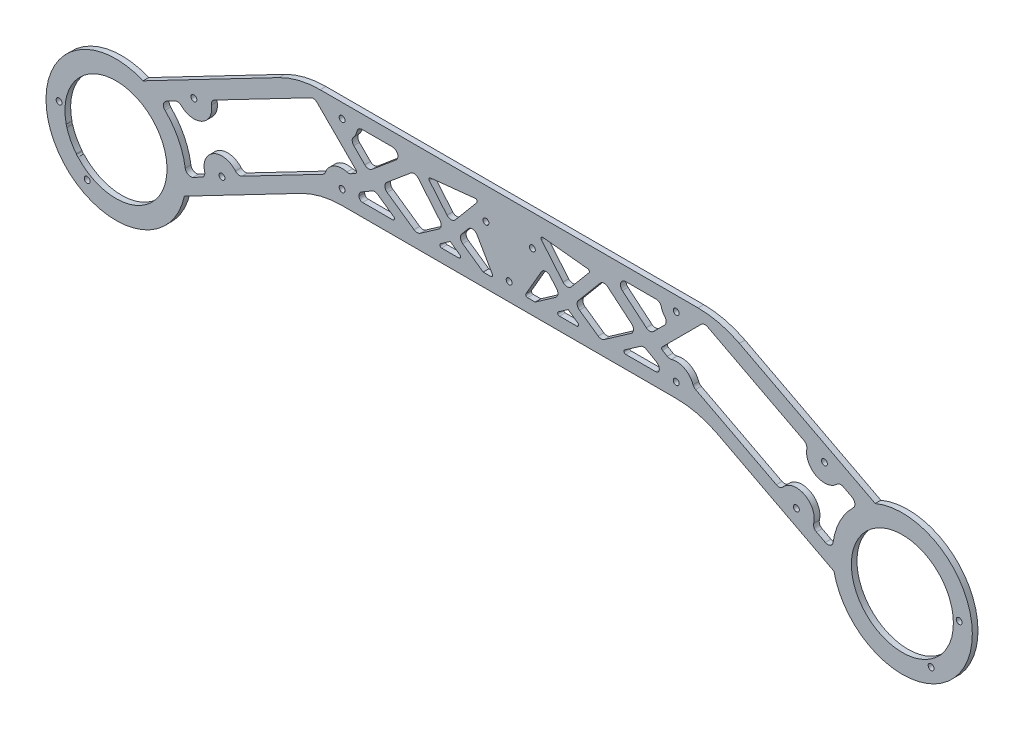
SolidWorks part; units mm, degrees
material "6061-T6 (SS)"
ref_plane "Front Plane" through (0, 0, 0) normal (0, 0, 1) x (1, 0, 0)
ref_plane "Top Plane" through (0, 0, 0) normal (0, 1, 0) x (1, 0, 0)
ref_plane "Right Plane" through (0, 0, 0) normal (1, 0, 0) x (0, 0, -1)
sketch "Sketch1" plane through (0, 0, 0) normal (0, 0, 1) x (1, 0, 0)
  line L0 (0, -33.2132) -> (0, -83.2132) construction
  line L1 (105.7091, -33.2132) -> (-105.7091, -33.2132)
  line L2 (-128.7965, -38.8627) -> (-262.5891, -108.5107)
  line L3 (-262.5891, -108.5107) -> (-239.5017, -152.8612)
  line L4 (-239.5017, -152.8612) -> (-116.5616, -88.8627)
  line L5 (-93.4741, -83.2132) -> (93.4741, -83.2132)
  line L6 (116.5616, -88.8627) -> (239.5017, -152.8612)
  line L7 (239.5017, -152.8612) -> (262.5891, -108.5107)
  line L8 (262.5891, -108.5107) -> (128.7965, -38.8627)
  line L9 (-117.944, -33.2132) -> (0, 28.1845) construction
  line L10 (0, 28.1845) -> (117.944, -33.2132) construction
  line L11 (-251.0454, -130.686) -> (-220, -114.5248) construction
  line L12 (251.0454, -130.686) -> (220, -114.5248) construction
  line L13 (-330, -114.5248) -> (-110, -114.5248) construction
  line L14 (-110, -114.5248) -> (110, -114.5248) construction
  line L15 (0, 0) -> (17.6777, -17.6777) construction
  line L16 (28.2843, -7.0711) -> (7.0711, -28.2843) construction
  line L17 (-7.0711, -28.2843) -> (-17.6777, -17.6777) construction
  line L18 (-17.6777, -17.6777) -> (17.6777, 17.6777) construction
  line L19 (17.6777, 17.6777) -> (28.2843, 7.0711) construction
  line L20 (17.6777, 17.6777) -> (67.5526, 17.6777) construction
  line L21 (0, -35.3553) -> (35.3553, 0) construction
  line L22 (0, 0) -> (6.4705, -24.1481) construction
  line L23 (-8.0184, -28.0304) -> (20.9594, -20.2659) construction
  circle A1 centre (0, 0) radius 7.9375 construction
  circle A2 centre (-220, -114.5248) radius 110 construction
  circle A3 centre (220, -114.5248) radius 110 construction
  arc A4 (28.2843, -7.0711) -> (28.2843, 7.0711) centre (21.2132, 0) ccw construction
  arc A5 (7.0711, -28.2843) -> (-7.0711, -28.2843) centre (0, -21.2132) cw construction
  arc A6 (93.4741, -83.2132) -> (116.5616, -88.8627) centre (93.4741, -133.2132) cw
  arc A7 (-116.5616, -88.8627) -> (-93.4741, -83.2132) centre (-93.4741, -133.2132) cw
  arc A8 (128.7965, -38.8627) -> (105.7091, -33.2132) centre (105.7091, -83.2132) ccw
  arc A9 (-105.7091, -33.2132) -> (-128.7965, -38.8627) centre (-105.7091, -83.2132) ccw
  circle A10 centre (0, 0) radius 7.9375 construction
  arc A11 (20.9594, -20.2659) -> (28.0304, -8.0184) centre (18.3712, -10.6066) ccw construction
  point P26 (17.6777, -17.6777)
  point P33 (35.3553, 0)
  point P36 (0, -35.3553)
  point P40 (0, -31.2132)
  dimension "D12" = 50
  dimension "D2" = 220
  dimension "D1" = 50
  dimension "D3" = 125
  dimension "D5" = 35
  dimension "D8" = 45
  dimension "D10" = 2
extrude "Base" add sketch "Sketch1" along normal blind 3.175
fillet "Fillet1" radius 10 4 edges at (262.5891, -108.5107, 1.5875) (239.5017, -152.8612, 1.5875) (-239.5017, -152.8612, 1.5875) (-262.5891, -108.5107, 1.5875)
sketch "Sketch2" plane through (0, 0, 3.175) normal (0, 0, 1) x (1, 0, 0)
  line L0 (0, -33.2132) -> (0, -83.2132) construction
  line L1 (105.7091, -33.2132) -> (-105.7091, -33.2132) construction
  line L2 (-93.4741, -83.2132) -> (93.4741, -83.2132) construction
  circle A0 centre (0, -58.2132) radius 15 construction
  circle A1 centre (-12.9904, -50.7132) radius 1.65
  circle A2 centre (12.9904, -50.7132) radius 1.65
  circle A3 centre (0, -73.2132) radius 1.65
  point P17 (0, -58.2132)
  dimension "D1" = 30
  dimension "D2" = 3.3
  dimension "D3" = 3
extrude "Adapter Attachment" cut sketch "Sketch2" against normal through all
sketch "Sketch3" plane through (0, 0, 3.175) normal (0, 0, 1) x (1, 0, 0)
  line L0 (-258.6387, -109.7562) -> (-249.1015, -112.7633) construction
  line L1 (-238.2561, -148.9108) -> (-235.249, -139.3736) construction
  line L2 (-251.799, -111.9128) -> (-255.493, -104.8167) construction
  line L3 (-236.0996, -142.0711) -> (-232.4056, -149.1672) construction
  line L4 (-128.7965, -38.8627) -> (-253.719, -103.8932) construction
  line L5 (-230.6316, -148.2437) -> (-116.5616, -88.8627) construction
  line L6 (0, -1.7463) -> (0, 1.7463) construction
  line L7 (-236.0996, -142.0711) -> (-160.7036, -102.8225) construction
  line L8 (-176.4031, -72.6641) -> (-251.799, -111.9128) construction
  line L9 (-93.4741, -83.2132) -> (-93.4741, -75.2132) construction
  line L10 (-93.4741, -83.2132) -> (93.4741, -83.2132) construction
  line L11 (-93.4741, -41.2132) -> (-93.4741, -33.2132) construction
  line L12 (105.7091, -33.2132) -> (-105.7091, -33.2132) construction
  arc A0 (-253.719, -103.8932) -> (-257.9716, -117.3808) centre (-249.1015, -112.7633) ccw construction
  arc A1 (-244.1191, -143.9911) -> (-230.6316, -148.2437) centre (-235.249, -139.3736) ccw construction
  circle A2 centre (-251.799, -111.9128) radius 1.65
  circle A3 centre (-236.0996, -142.0711) radius 1.65
  circle A4 centre (-160.7036, -102.8225) radius 1.65
  circle A5 centre (-176.4031, -72.6641) radius 1.65
  circle A6 centre (-93.4741, -75.2132) radius 1.65
  circle A7 centre (-93.4741, -41.2132) radius 1.65
  circle A8 centre (93.4741, -41.2132) radius 1.65
  circle A9 centre (93.4741, -75.2132) radius 1.65
  circle A10 centre (176.4031, -72.6641) radius 1.65
  circle A11 centre (160.7036, -102.8225) radius 1.65
  circle A12 centre (251.799, -111.9128) radius 1.65
  circle A13 centre (236.0996, -142.0711) radius 1.65
  dimension "D2" = 3.3
  dimension "D1" = 8
  dimension "D4" = 85
extrude "Strut Holes" cut sketch "Sketch3" against normal through all
sketch "Sketch4" plane through (0, 0, 3.175) normal (0, 0, 1) x (1, 0, 0)
  line L0 (-241.4586, -107.7589) -> (-213.2341, -93.0661) construction
  line L1 (-128.7965, -38.8627) -> (-262.5891, -108.5107) construction
  line L2 (0, -1.7463) -> (0, 1.7463) construction
  circle A0 centre (-220, -114.5248) radius 16.05
  circle A1 centre (-220, -114.5248) radius 22.5 construction
  circle A2 centre (-241.4586, -107.7589) radius 2.75
  circle A3 centre (-213.2341, -93.0661) radius 2.75
  circle A4 centre (-198.5414, -121.2906) radius 2.75
  circle A5 centre (-226.7659, -135.9834) radius 2.75
  circle A6 centre (226.7659, -135.9834) radius 2.75
  circle A7 centre (241.4586, -107.7589) radius 2.75
  circle A8 centre (198.5414, -121.2906) radius 2.75
  circle A9 centre (213.2341, -93.0661) radius 2.75
  circle A10 centre (220, -114.5248) radius 16.05
  point P15 (-220, -114.5248)
  dimension "D1" = 32.1
  dimension "D2" = 45
  dimension "D4" = 5.5
  dimension "D3" = 4
extrude "Motor Connection" cut sketch "Sketch4" against normal through all
sketch "Sketch5" plane through (0, 0, 3.175) normal (0, 0, 1) x (1, 0, 0)
  line L0 (0, -1.7463) -> (0, 1.7463) construction
  circle A0 centre (-220, -114.5248) radius 28.55
  circle A1 centre (-220, -114.5248) radius 39.1548
  arc A2 (-253.719, -103.8932) -> (-257.9716, -117.3808) centre (-249.1015, -112.7633) ccw construction
  circle A3 centre (-236.0996, -142.0711) radius 1.65 construction
  circle A4 centre (-251.799, -111.9128) radius 1.65 construction
  circle A5 centre (-236.0996, -142.0711) radius 1.65
  circle A6 centre (-251.799, -111.9128) radius 1.65
  circle A7 centre (251.799, -111.9128) radius 1.65
  circle A8 centre (236.0996, -142.0711) radius 1.65
  circle A9 centre (220, -114.5248) radius 39.1548
  circle A10 centre (220, -114.5248) radius 28.55
  line M20 (253.719, -103.8932) -> (128.7965, -38.8627)
  line M24 (-128.7965, -38.8627) -> (-253.719, -103.8932)
  line M28 (-230.6316, -148.2437) -> (-116.5616, -88.8627)
  line M32 (116.5616, -88.8627) -> (230.6316, -148.2437)
  dimension "D1" = 57.1
extrude "Motor Ring" add sketch "Sketch5" against normal up to surface (3.175 mm away) up to face at (-238.7086, -107.7589, 0)
extrude "Motor Slot" cut sketch "Sketch5<2>" against normal through all contours A0 M24 M28 | A10 M32 M20 region at (-220, -114.5248, 3.175) region at (220, -114.5248, 3.175)
sketch "Sketch5<2>" plane through (0, 0, 3.175) normal (0, 0, 1) x (1, 0, 0) same geometry as "Sketch5"
sketch "Sketch6" plane through (0, 0, 3.175) normal (0, 0, 1) x (1, 0, 0)
  line L0 (-247.6068, -122.1316) -> (-242.0658, -132.7758)
  line L1 (-239.3683, -133.6263) -> (-237.5943, -132.7028)
  line L2 (-236.7437, -130.0053) -> (-242.2847, -119.3612)
  line L3 (-244.9822, -118.5106) -> (-246.7563, -119.4341)
  line L4 (-251.799, -111.9128) -> (-236.0996, -142.0711) construction
  line L5 (-243.9493, -126.992) -> (-111.8265, -58.2132) construction
  line L6 (-111.8265, -58.2132) -> (0, -58.2132) construction
  line L7 (0, -33.2132) -> (0, -83.2132) construction
  line L8 (105.7091, -33.2132) -> (-105.7091, -33.2132) construction
  line L9 (-93.4741, -83.2132) -> (93.4741, -83.2132) construction
  line L10 (-14.5393, -75.9632) -> (-10.2714, -75.9632)
  line L12 (-14.5393, -75.9632) -> (-25.9975, -67.9401)
  line L13 (-26.5749, -63.5543) -> (-22.8888, -59.1614)
  line L14 (-28.1716, -75.9632) -> (-37.8284, -75.9632)
  line L15 (-38.402, -74.1441) -> (-33, -70.3615)
  line L16 (-33, -70.3615) -> (-27.598, -74.1441)
  line L17 (-18.9615, -42.4719) -> (-43.968, -45.1002)
  line L18 (-44.6295, -46.7375) -> (-34.7611, -58.4983)
  line L19 (-30.1648, -58.4983) -> (-18.091, -44.1092)
  line L20 (-50.8755, -48.6282) -> (-38.7485, -63.0805)
  line L21 (-39.3259, -67.4663) -> (-49.7793, -74.7859)
  line L22 (-53.2207, -74.7859) -> (-68.277, -64.2434)
  line L23 (-68.4846, -59.4878) -> (-55.102, -48.2584)
  line L24 (-9.4053, -74.4632) -> (-17.9925, -59.5897)
  line L25 (-14.4193, -51.5382) -> (-1.4289, -74.0382) construction
  line L26 (-64.598, -74.1441) -> (-73.5076, -67.9055)
  line L27 (-76.7283, -67.7649) -> (-82.5, -71.0972)
  line L28 (-84, -73.6953) -> (-84, -73.9632)
  line L29 (-82, -75.9632) -> (-65.1716, -75.9632)
  line L30 (-65.2424, -40.7132) -> (-82.2492, -40.7132)
  line L31 (-86.9487, -50.9163) -> (-80.7761, -57.0888)
  line L32 (-76.7264, -57.2656) -> (-63.3141, -46.0113)
  line L33 (-107.4845, -40.2799) -> (-85.5801, -62.1843)
  line L34 (-85.7872, -63.7574) -> (-88.4538, -65.297)
  line L35 (-110.9911, -39.7402) -> (-164.9696, -67.8396)
  line L36 (-128.7965, -38.8627) -> (-204.814, -78.4349) construction
  line L37 (-186.9131, -79.2627) -> (-191.8231, -81.8187)
  line L38 (-176.8853, -111.2462) -> (-171.9235, -108.6632)
  line L39 (-149.4837, -96.9818) -> (-104.3206, -73.4714)
  line L40 (-181.7266, -122.7854) -> (-116.5616, -88.8627) construction
  line L41 (149.4837, -96.9818) -> (104.3206, -73.4714)
  line L42 (176.8853, -111.2462) -> (171.9235, -108.6632)
  line L43 (186.9131, -79.2627) -> (191.8231, -81.8187)
  line L44 (110.9911, -39.7402) -> (164.9696, -67.8396)
  line L45 (85.7872, -63.7574) -> (88.4538, -65.297)
  line L46 (107.4845, -40.2799) -> (85.5801, -62.1843)
  line L47 (76.7264, -57.2656) -> (63.3141, -46.0113)
  line L48 (86.9487, -50.9163) -> (80.7761, -57.0888)
  line L49 (65.2424, -40.7132) -> (82.2492, -40.7132)
  line L50 (82, -75.9632) -> (65.1716, -75.9632)
  line L51 (84, -73.6953) -> (84, -73.9632)
  line L52 (76.7283, -67.7649) -> (82.5, -71.0972)
  line L53 (64.598, -74.1441) -> (73.5076, -67.9055)
  line L54 (9.4053, -74.4632) -> (17.9925, -59.5897)
  line L55 (68.4846, -59.4878) -> (55.102, -48.2584)
  line L56 (53.2207, -74.7859) -> (68.277, -64.2434)
  line L57 (39.3259, -67.4663) -> (49.7793, -74.7859)
  line L58 (50.8755, -48.6282) -> (38.7485, -63.0805)
  line L59 (30.1648, -58.4983) -> (18.091, -44.1092)
  line L60 (44.6295, -46.7375) -> (34.7611, -58.4983)
  line L61 (18.9615, -42.4719) -> (43.968, -45.1002)
  line L62 (33, -70.3615) -> (27.598, -74.1441)
  line L63 (38.402, -74.1441) -> (33, -70.3615)
  line L64 (28.1716, -75.9632) -> (37.8284, -75.9632)
  line L65 (26.5749, -63.5543) -> (22.8888, -59.1614)
  line L66 (14.5393, -75.9632) -> (25.9975, -67.9401)
  line L67 (14.5393, -75.9632) -> (10.2714, -75.9632)
  line L68 (244.9822, -118.5106) -> (246.7563, -119.4341)
  line L69 (236.7437, -130.0053) -> (242.2847, -119.3612)
  line L70 (239.3683, -133.6263) -> (237.5943, -132.7028)
  line L71 (247.6068, -122.1316) -> (242.0658, -132.7758)
  circle A0 centre (-12.9904, -50.7132) radius 1.65 construction
  circle A1 centre (0, -73.2132) radius 1.65 construction
  arc A2 (-85.1774, -43.061) -> (-87.083, -46.8171) centre (-93.4741, -41.2132) cw
  arc A3 (-90.7662, -65.5868) -> (-102.8831, -71.8264) centre (-93.4741, -75.2132) ccw
  arc A4 (-166.5426, -70.9999) -> (-183.4221, -79.7869) centre (-176.4031, -72.6641) cw
  arc A5 (-170.3999, -105.2684) -> (-153.1385, -96.2827) centre (-160.7036, -102.8225) cw
  arc A6 (-192.5419, -86.6182) -> (-181.2407, -109.0079) centre (-220, -114.5248) cw
  circle A7 centre (-220, -114.5248) radius 110 construction
  arc A8 (-85.5801, -62.1843) -> (-85.7872, -63.7574) centre (-86.2872, -62.8914) cw
  arc A9 (-43.968, -45.1002) -> (-44.6295, -46.7375) centre (-43.8634, -46.0947) ccw
  arc A10 (-18.091, -44.1092) -> (-18.9615, -42.4719) centre (-18.857, -43.4664) ccw
  arc A11 (-64.598, -74.1441) -> (-65.1716, -75.9632) centre (-65.1716, -74.9632) cw
  arc A12 (-37.8284, -75.9632) -> (-38.402, -74.1441) centre (-37.8284, -74.9632) cw
  arc A13 (-28.1716, -75.9632) -> (-27.598, -74.1441) centre (-28.1716, -74.9632) ccw
  arc A14 (-10.2714, -75.9632) -> (-9.4053, -74.4632) centre (-10.2714, -74.9632) ccw
  arc A15 (-181.2407, -109.0079) -> (-176.8853, -111.2462) centre (-178.2706, -108.5851) ccw
  arc A16 (-191.8231, -81.8187) -> (-192.5419, -86.6182) centre (-190.4379, -84.4797) ccw
  arc A17 (-171.9235, -108.6632) -> (-170.3999, -105.2684) centre (-173.3088, -106.0022) ccw
  arc A18 (-153.1385, -96.2827) -> (-149.4837, -96.9818) centre (-150.869, -94.3208) ccw
  arc A19 (-183.4221, -79.7869) -> (-186.9131, -79.2627) centre (-185.5278, -81.9237) ccw
  arc A20 (-164.9696, -67.8396) -> (-166.5426, -70.9999) centre (-163.5844, -70.5007) ccw
  arc A21 (-107.4845, -40.2799) -> (-110.9911, -39.7402) centre (-109.6058, -42.4012) ccw
  arc A22 (-102.8831, -71.8264) -> (-104.3206, -73.4714) centre (-105.7058, -70.8103) cw
  arc A23 (-88.4538, -65.297) -> (-90.7662, -65.5868) centre (-89.9538, -62.6989) cw
  arc A24 (-65.2424, -40.7132) -> (-63.3141, -46.0113) centre (-65.2424, -43.7132) cw
  arc A25 (-80.7761, -57.0888) -> (-76.7264, -57.2656) centre (-78.6548, -54.9675) ccw
  arc A26 (-82.2492, -40.7132) -> (-85.1774, -43.061) centre (-82.2492, -43.7132) ccw
  arc A27 (-87.083, -46.8171) -> (-86.9487, -50.9163) centre (-84.8273, -48.7949) ccw
  arc A28 (-82.5, -71.0972) -> (-84, -73.6953) centre (-81, -73.6953) ccw
  arc A29 (-73.5076, -67.9055) -> (-76.7283, -67.7649) centre (-75.2283, -70.363) ccw
  arc A30 (-50.8755, -48.6282) -> (-55.102, -48.2584) centre (-53.1736, -50.5565) ccw
  arc A31 (-68.277, -64.2434) -> (-68.4846, -59.4878) centre (-66.5562, -61.7859) cw
  arc A32 (-49.7793, -74.7859) -> (-53.2207, -74.7859) centre (-51.5, -72.3284) cw
  arc A33 (-38.7485, -63.0805) -> (-39.3259, -67.4663) centre (-41.0466, -65.0089) cw
  arc A34 (-34.7611, -58.4983) -> (-30.1648, -58.4983) centre (-32.4629, -56.5699) ccw
  arc A35 (-17.9925, -59.5897) -> (-22.8888, -59.1614) centre (-20.5906, -61.0897) ccw
  arc A36 (-25.9975, -67.9401) -> (-26.5749, -63.5543) centre (-24.2767, -65.4827) cw
  arc A37 (-242.2847, -119.3612) -> (-244.9822, -118.5106) centre (-244.0588, -120.2847) ccw
  arc A38 (-247.6068, -122.1316) -> (-246.7563, -119.4341) centre (-245.8328, -121.2082) cw
  arc A39 (-242.0658, -132.7758) -> (-239.3683, -133.6263) centre (-240.2918, -131.8523) ccw
  arc A40 (-237.5943, -132.7028) -> (-236.7437, -130.0053) centre (-238.5178, -130.9288) ccw
  arc A41 (-84, -73.9632) -> (-82, -75.9632) centre (-82, -73.9632) ccw
  arc A42 (84, -73.9632) -> (82, -75.9632) centre (82, -73.9632) cw
  arc A43 (237.5943, -132.7028) -> (236.7437, -130.0053) centre (238.5178, -130.9288) cw
  arc A44 (242.0658, -132.7758) -> (239.3683, -133.6263) centre (240.2918, -131.8523) cw
  arc A45 (247.6068, -122.1316) -> (246.7563, -119.4341) centre (245.8328, -121.2082) ccw
  arc A46 (242.2847, -119.3612) -> (244.9822, -118.5106) centre (244.0588, -120.2847) cw
  arc A47 (25.9975, -67.9401) -> (26.5749, -63.5543) centre (24.2767, -65.4827) ccw
  arc A48 (17.9925, -59.5897) -> (22.8888, -59.1614) centre (20.5906, -61.0897) cw
  arc A49 (34.7611, -58.4983) -> (30.1648, -58.4983) centre (32.4629, -56.5699) cw
  arc A50 (38.7485, -63.0805) -> (39.3259, -67.4663) centre (41.0466, -65.0089) ccw
  arc A51 (49.7793, -74.7859) -> (53.2207, -74.7859) centre (51.5, -72.3284) ccw
  arc A52 (68.277, -64.2434) -> (68.4846, -59.4878) centre (66.5562, -61.7859) ccw
  arc A53 (50.8755, -48.6282) -> (55.102, -48.2584) centre (53.1736, -50.5565) cw
  arc A54 (73.5076, -67.9055) -> (76.7283, -67.7649) centre (75.2283, -70.363) cw
  arc A55 (82.5, -71.0972) -> (84, -73.6953) centre (81, -73.6953) cw
  arc A56 (87.083, -46.8171) -> (86.9487, -50.9163) centre (84.8273, -48.7949) cw
  arc A57 (82.2492, -40.7132) -> (85.1774, -43.061) centre (82.2492, -43.7132) cw
  arc A58 (80.7761, -57.0888) -> (76.7264, -57.2656) centre (78.6548, -54.9675) cw
  arc A59 (65.2424, -40.7132) -> (63.3141, -46.0113) centre (65.2424, -43.7132) ccw
  arc A60 (88.4538, -65.297) -> (90.7662, -65.5868) centre (89.9538, -62.6989) ccw
  arc A61 (102.8831, -71.8264) -> (104.3206, -73.4714) centre (105.7058, -70.8103) ccw
  arc A62 (107.4845, -40.2799) -> (110.9911, -39.7402) centre (109.6058, -42.4012) cw
  arc A63 (164.9696, -67.8396) -> (166.5426, -70.9999) centre (163.5844, -70.5007) cw
  arc A64 (183.4221, -79.7869) -> (186.9131, -79.2627) centre (185.5278, -81.9237) cw
  arc A65 (153.1385, -96.2827) -> (149.4837, -96.9818) centre (150.869, -94.3208) cw
  arc A66 (171.9235, -108.6632) -> (170.3999, -105.2684) centre (173.3088, -106.0022) cw
  arc A67 (191.8231, -81.8187) -> (192.5419, -86.6182) centre (190.4379, -84.4797) cw
  arc A68 (181.2407, -109.0079) -> (176.8853, -111.2462) centre (178.2706, -108.5851) cw
  arc A69 (10.2714, -75.9632) -> (9.4053, -74.4632) centre (10.2714, -74.9632) cw
  arc A70 (28.1716, -75.9632) -> (27.598, -74.1441) centre (28.1716, -74.9632) cw
  arc A71 (37.8284, -75.9632) -> (38.402, -74.1441) centre (37.8284, -74.9632) ccw
  arc A72 (64.598, -74.1441) -> (65.1716, -75.9632) centre (65.1716, -74.9632) ccw
  arc A73 (18.091, -44.1092) -> (18.9615, -42.4719) centre (18.857, -43.4664) cw
  arc A74 (43.968, -45.1002) -> (44.6295, -46.7375) centre (43.8634, -46.0947) cw
  arc A75 (85.5801, -62.1843) -> (85.7872, -63.7574) centre (86.2872, -62.8914) ccw
  arc A76 (192.5419, -86.6182) -> (181.2407, -109.0079) centre (220, -114.5248) ccw
  arc A77 (170.3999, -105.2684) -> (153.1385, -96.2827) centre (160.7036, -102.8225) ccw
  arc A78 (166.5426, -70.9999) -> (183.4221, -79.7869) centre (176.4031, -72.6641) ccw
  arc A79 (90.7662, -65.5868) -> (102.8831, -71.8264) centre (93.4741, -75.2132) cw
  arc A80 (85.1774, -43.061) -> (87.083, -46.8171) centre (93.4741, -41.2132) ccw
  point P14 (-244.8363, -127.4537)
  point P75 (-45.8384, -45.2968)
  point P78 (-16.5, -42.2132)
  point P81 (-62, -75.9632)
  point P84 (-41, -75.9632)
  point P87 (-25, -75.9632)
  point P90 (-8.5393, -75.9632)
  point P111 (-57, -40.7132)
  point P114 (-78.8323, -59.0327)
  point P121 (-84, -71.9632)
  point P140 (-243.2082, -117.5871)
  point P143 (-248.5303, -120.3576)
  point P146 (-241.1423, -134.5498)
  point P151 (-84, -75.9632)
  point P261 (84, -75.9632)
  point P262 (241.1423, -134.5498)
  point P263 (248.5303, -120.3576)
  point P264 (243.2082, -117.5871)
  point P265 (84, -71.9632)
  point P266 (78.8323, -59.0327)
  point P267 (57, -40.7132)
  point P268 (8.5393, -75.9632)
  point P269 (25, -75.9632)
  point P270 (41, -75.9632)
  point P271 (62, -75.9632)
  point P272 (16.5, -42.2132)
  point P273 (45.8384, -45.2968)
  dimension "D29" = 8.5
  dimension "D35" = 39.15
  dimension "D37" = 10
  dimension "D38" = 1
  dimension "D39" = 3
  dimension "D40" = 2
  dimension "D1" = 1
  dimension "D2" = 6
  dimension "D3" = 16
  dimension "D4" = 16
  dimension "D5" = 50
  dimension "D6" = 7.25
  dimension "D7" = 25
  dimension "D8" = 35
  dimension "D9" = 6
  dimension "D10" = 6
  dimension "D11" = 9
  dimension "D12" = 16.5
  dimension "D13" = 50
  dimension "D14" = 29.5
  dimension "D15" = 6
  dimension "D16" = 6
  dimension "D17" = 6
  dimension "D18" = 6
  dimension "D19" = 35
  dimension "D20" = 62
  dimension "D21" = 22
  dimension "D22" = 30
  dimension "D23" = 6
  dimension "D24" = 4
  dimension "D25" = 7.5
  dimension "D26" = 57
  dimension "D27" = 40
  dimension "D28" = 45
  dimension "D30" = 28.5
  dimension "D31" = 7
  dimension "D32" = 8
  dimension "D33" = 7
  dimension "D34" = 9
  dimension "D36" = 8
extrude "Lightening Holes" cut sketch "Sketch6" against normal through all
equation "\"D2@Sketch1\" = \"Wheel Diameter@Rocker Bogie Assy-1.Assembly\""
equation "\"D1@Base\" = \"Plate Thickness@Rocker Bogie Assy-1.Assembly\""
equation "\"D3@Sketch1\"= \"Bogie Angle@Rocker Bogie Assy-1.Assembly\""
